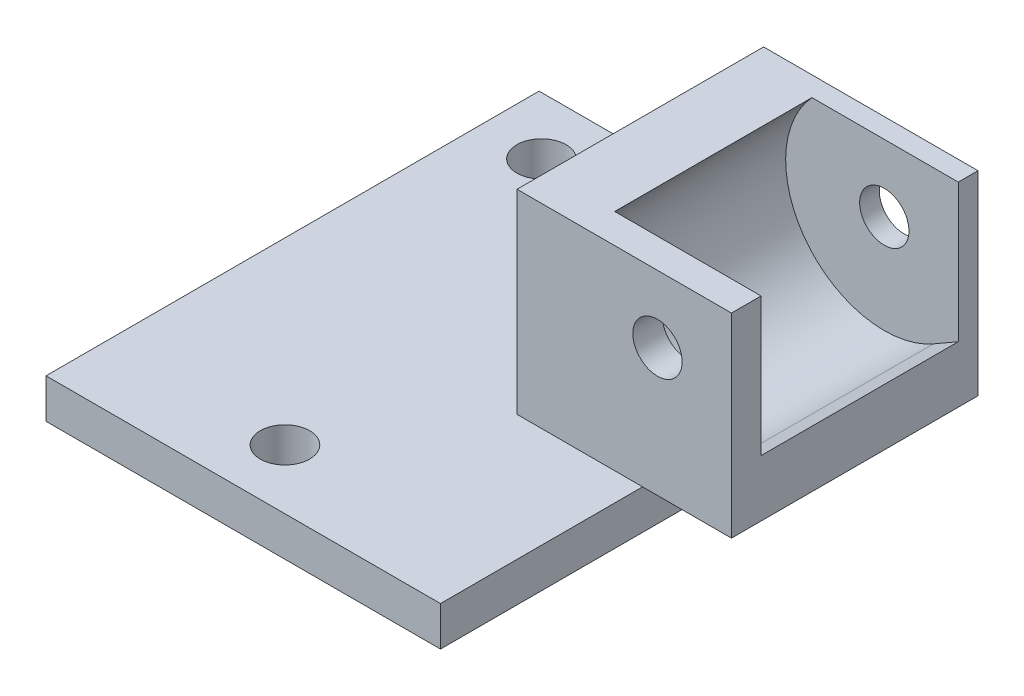
SolidWorks part; units mm, degrees
ref_plane "Front Plane" through (0, 0, 0) normal (0, 0, 1) x (1, 0, 0)
ref_plane "Top Plane" through (0, 0, 0) normal (0, 1, 0) x (1, 0, 0)
ref_plane "Right Plane" through (0, 0, 0) normal (1, 0, 0) x (0, 0, -1)
sketch "Sketch1" plane through (0, 0, 0) normal (0, 0, 1) x (1, 0, 0)
  line L0 (-527.7276, 348.6336) -> (-500.1158, 348.6336)
  line L1 (-500.1158, 348.6336) -> (-500.1158, 323.526)
  line L2 (-500.1158, 323.526) -> (-527.7276, 323.526)
  line L3 (-527.7276, 323.526) -> (-527.7276, 348.6336)
  line L4 (-471.0414, 347.5416) -> (-503.3159, 328.9895) construction
  line L5 (-471.0414, 347.5416) -> (-503.3159, 328.9895)
  arc A0 (-508.6898, 327.336) -> (-503.3159, 328.9895) centre (-509.645, 340) ccw construction
  arc A1 (-515.9742, 351.0105) -> (-520.1076, 347.199) centre (-509.645, 340) ccw construction
  arc A2 (-520.1076, 347.199) -> (-508.6898, 327.336) centre (-509.645, 340) ccw construction
  arc A3 (-508.6898, 327.336) -> (-503.3159, 328.9895) centre (-509.645, 340) ccw
  arc A4 (-515.9742, 351.0105) -> (-520.1076, 347.199) centre (-509.645, 340) ccw
  arc A5 (-520.1076, 347.199) -> (-508.6898, 327.336) centre (-509.645, 340) ccw
  dimension "D1" = 3.81
  dimension "D2" = 7.62
  dimension "D3" = 25.1076
  dimension "D4" = 27.6118
extrude "Boss-Extrude1" add sketch "Sketch1" against normal blind 27.94 contours A5 A4 L0 L3 L2 L1 L5 A3 region at (-523.3433, 348.2604, 0)
sketch "Sketch2" plane through (0, 0, -25.4) normal (0, 0, -1) x (-1, 0, 0)
  line L0 (500.1158, 330.829) -> (500.1158, 348.6336)
  line L1 (500.1158, 348.6336) -> (518.9591, 348.6336)
  line L2 (500.1158, 330.829) -> (503.3159, 328.9895) construction
  line L3 (500.1158, 330.829) -> (503.3159, 328.9895)
  arc A0 (503.3159, 328.9895) -> (518.9591, 348.6336) centre (509.645, 340) ccw construction
  arc A1 (503.3159, 328.9895) -> (518.9591, 348.6336) centre (509.645, 340) ccw
  circle A2 centre (509.645, 340) radius 3.175
  dimension "D1" = 6.35
extrude "Boss-Extrude2" add sketch "Sketch2" along normal up to surface (2.54 mm away) up to face at (-514.4007, 332.9024, -27.94)
sketch "Sketch3" plane through (0, 0, 0) normal (0, 0, 1) x (1, 0, 0)
  line L0 (-527.7276, 348.6336) -> (-500.1158, 348.6336)
  line L1 (-500.1158, 348.6336) -> (-500.1158, 323.526)
  line L2 (-500.1158, 323.526) -> (-527.7276, 323.526)
  line L3 (-527.7276, 323.526) -> (-527.7276, 348.6336)
  circle A0 centre (-509.645, 340) radius 3.175
  dimension "D1" = 6.35
extrude "Boss-Extrude3" add sketch "Sketch3" along normal blind 3.81 contours L3 L0 L1 L2 | A0
ref_plane "Plane1" through (0, 323.526, 0) normal (0, 1, 0) x (1, 0, 0)
sketch "Sketch4" plane through (0, 323.526, 0) normal (0, 1, 0) x (1, 0, 0)
  line L1 (-562.3598, 33.6602) -> (-511.5598, 33.7024)
  line L2 (-562.3598, 33.6602) -> (-562.3598, -29.8398)
  line L3 (-562.3598, -29.8398) -> (-511.5598, -29.8398)
  line L4 (-511.5598, 33.7024) -> (-511.5598, -29.8398)
  circle A0 centre (-539.2691, -22.1596) radius 3.175
  circle A1 centre (-554.6451, 26.2575) radius 3.175
  point P4 (-539.2691, -22.1596)
  point P5 (-554.6451, 26.2575)
  point P6 (-562.3598, 49.53)
  point P7 (-562.3598, -25.3346)
  point P8 (-512.4876, -29.8398)
  point P9 (-512.4876, 33.7024)
  point P16 (-562.3598, 33.7024)
  dimension "D5" = 50.8
  dimension "D9" = 6.35
  dimension "D10" = 6.35
  dimension "D2" = 63.5
  dimension "D3" = 63.5422
  dimension "D4" = 50.8
  dimension "D6" = 7.7147
  dimension "D7" = 7.6801
  dimension "D8" = 23.0907
extrude "Boss-Extrude4" add sketch "Sketch4" against normal blind 5.08
